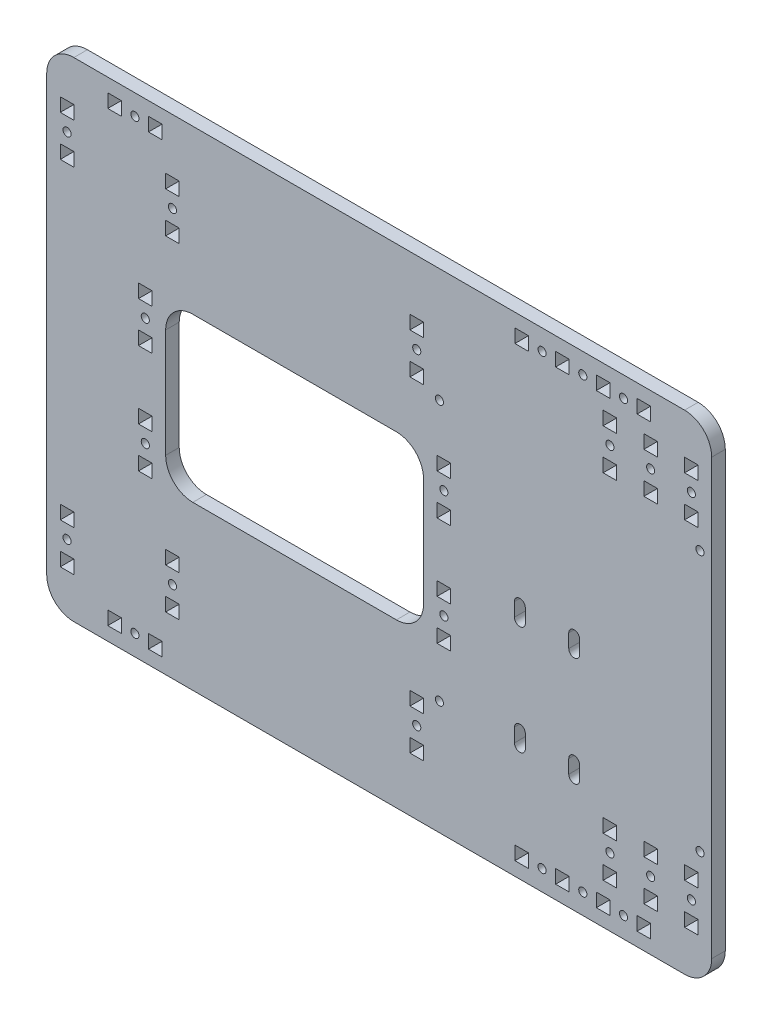
SolidWorks part; units mm, degrees
ref_plane "Front Plane" through (0, 0, 0) normal (0, 0, 1) x (1, 0, 0)
ref_plane "Top Plane" through (0, 0, 0) normal (0, 1, 0) x (1, 0, 0)
ref_plane "Right Plane" through (0, 0, 0) normal (1, 0, 0) x (0, 0, -1)
sketch "Sketch1" plane through (0, 0, 0) normal (0, 0, 1) x (1, 0, 0)
  line L0 (0, 0) -> (264.3375, 0) construction
  line L1 (-91.3244, 90) -> (153.676, 90)
  line L3 (-91.3244, -90) -> (153.676, -90)
  line L5 (23.6756, 97.7888) -> (23.6756, -107.1048) construction
  line L6 (-92.4996, 82.5) -> (92.5, 82.5) construction
  line L7 (92.5, -82.5) -> (-92.4996, -82.5) construction
  line L8 (-91.3244, 90) -> (-91.3244, -90)
  line L17 (53.355, -48) -> (53.355, 48) construction
  line L29 (53.355, -48) -> (149.355, -48) construction
  line L49 (53.355, 48) -> (149.355, 48) construction
  line L50 (149.355, -48) -> (149.355, 48) construction
  line L51 (-83.8244, 77.0051) -> (-83.8244, -67.4641) construction
  line L97 (-47.5, 30) -> (47.5, 30)
  line L98 (-47.5, 30) -> (-47.5, -30)
  line L99 (-47.5, -30) -> (47.5, -30)
  line L100 (47.5, 30) -> (47.5, -30)
  line L105 (103, -45) -> (49.07, -45) construction
  line L106 (103, -4.9002) -> (73.57, -4.9002) construction
  line L107 (103, -4.9002) -> (103, -45) construction
  line L108 (103, -7.4002) -> (103, -2.4002) construction
  line L109 (101, -7.4002) -> (101, -2.4002)
  line L110 (105, -7.4002) -> (105, -2.4002)
  line L111 (83, -7.4002) -> (83, -2.4002) construction
  line L112 (81, -7.4002) -> (81, -2.4002)
  line L113 (85, -7.4002) -> (85, -2.4002)
  line L114 (83, -47.5) -> (83, -42.5) construction
  line L115 (81, -47.5) -> (81, -42.5)
  line L116 (85, -47.5) -> (85, -42.5)
  line L117 (103, -47.5) -> (103, -42.5) construction
  line L118 (101, -47.5) -> (101, -42.5)
  line L119 (105, -47.5) -> (105, -42.5)
  line L122 (153.676, 90) -> (153.676, -90)
  line L124 (-83.8244, 65) -> (153.676, 65) construction
  line L125 (-83.8244, -65) -> (153.676, -65) construction
  line L126 (55, -20) -> (55, 20) construction
  arc A4 (101, -7.4002) -> (105, -7.4002) centre (103, -7.4002) ccw
  arc A5 (105, -2.4002) -> (101, -2.4002) centre (103, -2.4002) ccw
  arc A6 (81, -7.4002) -> (85, -7.4002) centre (83, -7.4002) ccw
  arc A7 (85, -2.4002) -> (81, -2.4002) centre (83, -2.4002) ccw
  arc A8 (81, -47.5) -> (85, -47.5) centre (83, -47.5) ccw
  arc A9 (85, -42.5) -> (81, -42.5) centre (83, -42.5) ccw
  arc A10 (101, -47.5) -> (105, -47.5) centre (103, -47.5) ccw
  arc A11 (105, -42.5) -> (101, -42.5) centre (103, -42.5) ccw
  circle A12 centre (53.355, 48) radius 1.5
  circle A13 centre (149.355, 48) radius 1.5
  circle A14 centre (149.355, -48) radius 1.5
  circle A15 centre (53.355, -48) radius 1.5
  point P21 (124, -51.7759)
  point P26 (103, -45.0347)
  point P113 (103, -4.9002)
  point P122 (83, -4.9002)
  point P129 (83, -45)
  point P136 (103, -45)
  line B0 (-63.8248, 82.5) -> (-53.8248, 82.5) construction
  line B1 (-63.8248, 85) -> (-68.8248, 85)
  line B2 (-63.8248, 85) -> (-63.8248, 80)
  line B3 (-63.8248, 80) -> (-68.8248, 80)
  line B4 (-68.8248, 85) -> (-68.8248, 80)
  line B5 (-53.8248, 85) -> (-48.8248, 85)
  line B6 (-53.8248, 85) -> (-53.8248, 80)
  line B7 (-53.8248, 80) -> (-48.8248, 80)
  line B8 (-48.8248, 85) -> (-48.8248, 80)
  line B9 (-58.8248, 82.5) -> (-58.8248, 89.4724) construction
  circle B10 centre (-58.8248, 82.5) radius 1.5
  line B11 (111.176, 82.5) -> (101.176, 82.5) construction
  line B12 (111.176, 85) -> (116.176, 85)
  line B13 (111.176, 85) -> (111.176, 80)
  line B14 (111.176, 80) -> (116.176, 80)
  line B15 (116.176, 85) -> (116.176, 80)
  line B16 (101.176, 85) -> (96.176, 85)
  line B17 (101.176, 85) -> (101.176, 80)
  line B18 (101.176, 80) -> (96.176, 80)
  line B19 (96.176, 85) -> (96.176, 80)
  line B20 (106.176, 82.5) -> (106.176, 89.4724) construction
  circle B21 centre (106.176, 82.5) radius 1.5
  line B22 (111.176, -82.5) -> (101.176, -82.5) construction
  line B23 (111.176, -85) -> (116.176, -85)
  line B24 (111.176, -85) -> (111.176, -80)
  line B25 (111.176, -80) -> (116.176, -80)
  line B26 (116.176, -85) -> (116.176, -80)
  line B27 (101.176, -85) -> (96.176, -85)
  line B28 (101.176, -85) -> (101.176, -80)
  line B29 (101.176, -80) -> (96.176, -80)
  line B30 (96.176, -85) -> (96.176, -80)
  line B31 (106.176, -82.5) -> (106.176, -89.4724) construction
  circle B32 centre (106.176, -82.5) radius 1.5
  line B33 (-63.8248, -82.5) -> (-53.8248, -82.5) construction
  line B34 (-63.8248, -85) -> (-68.8248, -85)
  line B35 (-63.8248, -85) -> (-63.8248, -80)
  line B36 (-63.8248, -80) -> (-68.8248, -80)
  line B37 (-68.8248, -85) -> (-68.8248, -80)
  line B38 (-53.8248, -85) -> (-48.8248, -85)
  line B39 (-53.8248, -85) -> (-53.8248, -80)
  line B40 (-53.8248, -80) -> (-48.8248, -80)
  line B41 (-48.8248, -85) -> (-48.8248, -80)
  line B42 (-58.8248, -82.5) -> (-58.8248, -89.4724) construction
  circle B43 centre (-58.8248, -82.5) radius 1.5
  line B44 (55, 25) -> (55, 15) construction
  line B45 (57.5, 25) -> (57.5, 30)
  line B46 (57.5, 25) -> (52.5, 25)
  line B47 (52.5, 25) -> (52.5, 30)
  line B48 (57.5, 30) -> (52.5, 30)
  line B49 (57.5, 15) -> (57.5, 10)
  line B50 (57.5, 15) -> (52.5, 15)
  line B51 (52.5, 15) -> (52.5, 10)
  line B52 (57.5, 10) -> (52.5, 10)
  line B53 (55, 20) -> (61.9724, 20) construction
  circle B54 centre (55, 20) radius 1.5
  line B55 (-55, 25) -> (-55, 15) construction
  line B56 (-57.5, 25) -> (-57.5, 30)
  line B57 (-57.5, 25) -> (-52.5, 25)
  line B58 (-52.5, 25) -> (-52.5, 30)
  line B59 (-57.5, 30) -> (-52.5, 30)
  line B60 (-57.5, 15) -> (-57.5, 10)
  line B61 (-57.5, 15) -> (-52.5, 15)
  line B62 (-52.5, 15) -> (-52.5, 10)
  line B63 (-57.5, 10) -> (-52.5, 10)
  line B64 (-55, 20) -> (-61.9724, 20) construction
  circle B65 centre (-55, 20) radius 1.5
  line B66 (55, -25) -> (55, -15) construction
  line B67 (57.5, -25) -> (57.5, -30)
  line B68 (57.5, -25) -> (52.5, -25)
  line B69 (52.5, -25) -> (52.5, -30)
  line B70 (57.5, -30) -> (52.5, -30)
  line B71 (57.5, -15) -> (57.5, -10)
  line B72 (57.5, -15) -> (52.5, -15)
  line B73 (52.5, -15) -> (52.5, -10)
  line B74 (57.5, -10) -> (52.5, -10)
  line B75 (55, -20) -> (61.9724, -20) construction
  circle B76 centre (55, -20) radius 1.5
  line B77 (-55, -25) -> (-55, -15) construction
  line B78 (-57.5, -25) -> (-57.5, -30)
  line B79 (-57.5, -25) -> (-52.5, -25)
  line B80 (-52.5, -25) -> (-52.5, -30)
  line B81 (-57.5, -30) -> (-52.5, -30)
  line B82 (-57.5, -15) -> (-57.5, -10)
  line B83 (-57.5, -15) -> (-52.5, -15)
  line B84 (-52.5, -15) -> (-52.5, -10)
  line B85 (-57.5, -10) -> (-52.5, -10)
  line B86 (-55, -20) -> (-61.9724, -20) construction
  circle B87 centre (-55, -20) radius 1.5
  line B88 (45, 65) -> (45, 55) construction
  line B89 (47.5, 65) -> (47.5, 70)
  line B90 (47.5, 65) -> (42.5, 65)
  line B91 (42.5, 65) -> (42.5, 70)
  line B92 (47.5, 70) -> (42.5, 70)
  line B93 (47.5, 55) -> (47.5, 50)
  line B94 (47.5, 55) -> (42.5, 55)
  line B95 (42.5, 55) -> (42.5, 50)
  line B96 (47.5, 50) -> (42.5, 50)
  line B97 (45, 60) -> (51.9724, 60) construction
  circle B98 centre (45, 60) radius 1.5
  line B99 (-45, 65) -> (-45, 55) construction
  line B100 (-47.5, 65) -> (-47.5, 70)
  line B101 (-47.5, 65) -> (-42.5, 65)
  line B102 (-42.5, 65) -> (-42.5, 70)
  line B103 (-47.5, 70) -> (-42.5, 70)
  line B104 (-47.5, 55) -> (-47.5, 50)
  line B105 (-47.5, 55) -> (-42.5, 55)
  line B106 (-42.5, 55) -> (-42.5, 50)
  line B107 (-47.5, 50) -> (-42.5, 50)
  line B108 (-45, 60) -> (-51.9724, 60) construction
  circle B109 centre (-45, 60) radius 1.5
  line B110 (45, -65) -> (45, -55) construction
  line B111 (47.5, -65) -> (47.5, -70)
  line B112 (47.5, -65) -> (42.5, -65)
  line B113 (42.5, -65) -> (42.5, -70)
  line B114 (47.5, -70) -> (42.5, -70)
  line B115 (47.5, -55) -> (47.5, -50)
  line B116 (47.5, -55) -> (42.5, -55)
  line B117 (42.5, -55) -> (42.5, -50)
  line B118 (47.5, -50) -> (42.5, -50)
  line B119 (45, -60) -> (51.9724, -60) construction
  circle B120 centre (45, -60) radius 1.5
  line B121 (-45, -65) -> (-45, -55) construction
  line B122 (-47.5, -65) -> (-47.5, -70)
  line B123 (-47.5, -65) -> (-42.5, -65)
  line B124 (-42.5, -65) -> (-42.5, -70)
  line B125 (-47.5, -70) -> (-42.5, -70)
  line B126 (-47.5, -55) -> (-47.5, -50)
  line B127 (-47.5, -55) -> (-42.5, -55)
  line B128 (-42.5, -55) -> (-42.5, -50)
  line B129 (-47.5, -50) -> (-42.5, -50)
  line B130 (-45, -60) -> (-51.9724, -60) construction
  circle B131 centre (-45, -60) radius 1.5
  line B132 (96.176, 82.5) -> (86.176, 82.5) construction
  line B133 (96.176, 85) -> (101.176, 85)
  line B134 (96.176, 85) -> (96.176, 80)
  line B135 (96.176, 80) -> (101.176, 80)
  line B136 (101.176, 85) -> (101.176, 80)
  line B137 (86.176, 85) -> (81.176, 85)
  line B138 (86.176, 85) -> (86.176, 80)
  line B139 (86.176, 80) -> (81.176, 80)
  line B140 (81.176, 85) -> (81.176, 80)
  line B141 (91.176, 82.5) -> (91.176, 89.4724) construction
  circle B142 centre (91.176, 82.5) radius 1.5
  line B143 (126.176, 82.5) -> (116.176, 82.5) construction
  line B144 (126.176, 85) -> (131.176, 85)
  line B145 (126.176, 85) -> (126.176, 80)
  line B146 (126.176, 80) -> (131.176, 80)
  line B147 (131.176, 85) -> (131.176, 80)
  line B148 (116.176, 85) -> (111.176, 85)
  line B149 (116.176, 85) -> (116.176, 80)
  line B150 (116.176, 80) -> (111.176, 80)
  line B151 (111.176, 85) -> (111.176, 80)
  line B152 (121.176, 82.5) -> (121.176, 89.4724) construction
  circle B153 centre (121.176, 82.5) radius 1.5
  line B154 (96.176, -82.5) -> (86.176, -82.5) construction
  line B155 (96.176, -85) -> (101.176, -85)
  line B156 (96.176, -85) -> (96.176, -80)
  line B157 (96.176, -80) -> (101.176, -80)
  line B158 (101.176, -85) -> (101.176, -80)
  line B159 (86.176, -85) -> (81.176, -85)
  line B160 (86.176, -85) -> (86.176, -80)
  line B161 (86.176, -80) -> (81.176, -80)
  line B162 (81.176, -85) -> (81.176, -80)
  line B163 (91.176, -82.5) -> (91.176, -89.4724) construction
  circle B164 centre (91.176, -82.5) radius 1.5
  line B165 (126.176, -82.5) -> (116.176, -82.5) construction
  line B166 (126.176, -85) -> (131.176, -85)
  line B167 (126.176, -85) -> (126.176, -80)
  line B168 (126.176, -80) -> (131.176, -80)
  line B169 (131.176, -85) -> (131.176, -80)
  line B170 (116.176, -85) -> (111.176, -85)
  line B171 (116.176, -85) -> (116.176, -80)
  line B172 (116.176, -80) -> (111.176, -80)
  line B173 (111.176, -85) -> (111.176, -80)
  line B174 (121.176, -82.5) -> (121.176, -89.4724) construction
  circle B175 centre (121.176, -82.5) radius 1.5
  line B176 (-83.8244, 70) -> (-83.8244, 60) construction
  line B177 (-86.3244, 70) -> (-86.3244, 75)
  line B178 (-86.3244, 70) -> (-81.3244, 70)
  line B179 (-81.3244, 70) -> (-81.3244, 75)
  line B180 (-86.3244, 75) -> (-81.3244, 75)
  line B181 (-86.3244, 60) -> (-86.3244, 55)
  line B182 (-86.3244, 60) -> (-81.3244, 60)
  line B183 (-81.3244, 60) -> (-81.3244, 55)
  line B184 (-86.3244, 55) -> (-81.3244, 55)
  line B185 (-83.8244, 65) -> (-90.7968, 65) construction
  circle B186 centre (-83.8244, 65) radius 1.5
  line B187 (-83.8244, -60) -> (-83.8244, -70) construction
  line B188 (-86.3244, -60) -> (-86.3244, -55)
  line B189 (-86.3244, -60) -> (-81.3244, -60)
  line B190 (-81.3244, -60) -> (-81.3244, -55)
  line B191 (-86.3244, -55) -> (-81.3244, -55)
  line B192 (-86.3244, -70) -> (-86.3244, -75)
  line B193 (-86.3244, -70) -> (-81.3244, -70)
  line B194 (-81.3244, -70) -> (-81.3244, -75)
  line B195 (-86.3244, -75) -> (-81.3244, -75)
  line B196 (-83.8244, -65) -> (-90.7968, -65) construction
  circle B197 centre (-83.8244, -65) radius 1.5
  line B198 (146.176, 70) -> (146.176, 60) construction
  line B199 (143.676, 70) -> (143.676, 75)
  line B200 (143.676, 70) -> (148.676, 70)
  line B201 (148.676, 70) -> (148.676, 75)
  line B202 (143.676, 75) -> (148.676, 75)
  line B203 (143.676, 60) -> (143.676, 55)
  line B204 (143.676, 60) -> (148.676, 60)
  line B205 (148.676, 60) -> (148.676, 55)
  line B206 (143.676, 55) -> (148.676, 55)
  line B207 (146.176, 65) -> (139.2036, 65) construction
  circle B208 centre (146.176, 65) radius 1.5
  line B209 (146.176, -60) -> (146.176, -70) construction
  line B210 (143.676, -60) -> (143.676, -55)
  line B211 (143.676, -60) -> (148.676, -60)
  line B212 (148.676, -60) -> (148.676, -55)
  line B213 (143.676, -55) -> (148.676, -55)
  line B214 (143.676, -70) -> (143.676, -75)
  line B215 (143.676, -70) -> (148.676, -70)
  line B216 (148.676, -70) -> (148.676, -75)
  line B217 (143.676, -75) -> (148.676, -75)
  line B218 (146.176, -65) -> (139.2036, -65) construction
  circle B219 centre (146.176, -65) radius 1.5
  line B220 (131.176, -60) -> (131.176, -70) construction
  line B221 (128.676, -60) -> (128.676, -55)
  line B222 (128.676, -60) -> (133.676, -60)
  line B223 (133.676, -60) -> (133.676, -55)
  line B224 (128.676, -55) -> (133.676, -55)
  line B225 (128.676, -70) -> (128.676, -75)
  line B226 (128.676, -70) -> (133.676, -70)
  line B227 (133.676, -70) -> (133.676, -75)
  line B228 (128.676, -75) -> (133.676, -75)
  line B229 (131.176, -65) -> (124.2036, -65) construction
  circle B230 centre (131.176, -65) radius 1.5
  line B231 (116.176, -60) -> (116.176, -70) construction
  line B232 (113.676, -60) -> (113.676, -55)
  line B233 (113.676, -60) -> (118.676, -60)
  line B234 (118.676, -60) -> (118.676, -55)
  line B235 (113.676, -55) -> (118.676, -55)
  line B236 (113.676, -70) -> (113.676, -75)
  line B237 (113.676, -70) -> (118.676, -70)
  line B238 (118.676, -70) -> (118.676, -75)
  line B239 (113.676, -75) -> (118.676, -75)
  line B240 (116.176, -65) -> (109.2036, -65) construction
  circle B241 centre (116.176, -65) radius 1.5
  line B242 (131.176, 70) -> (131.176, 60) construction
  line B243 (128.676, 70) -> (128.676, 75)
  line B244 (128.676, 70) -> (133.676, 70)
  line B245 (133.676, 70) -> (133.676, 75)
  line B246 (128.676, 75) -> (133.676, 75)
  line B247 (128.676, 60) -> (128.676, 55)
  line B248 (128.676, 60) -> (133.676, 60)
  line B249 (133.676, 60) -> (133.676, 55)
  line B250 (128.676, 55) -> (133.676, 55)
  line B251 (131.176, 65) -> (124.2036, 65) construction
  circle B252 centre (131.176, 65) radius 1.5
  line B253 (116.176, 70) -> (116.176, 60) construction
  line B254 (113.676, 70) -> (113.676, 75)
  line B255 (113.676, 70) -> (118.676, 70)
  line B256 (118.676, 70) -> (118.676, 75)
  line B257 (113.676, 75) -> (118.676, 75)
  line B258 (113.676, 60) -> (113.676, 55)
  line B259 (113.676, 60) -> (118.676, 60)
  line B260 (118.676, 60) -> (118.676, 55)
  line B261 (113.676, 55) -> (118.676, 55)
  line B262 (116.176, 65) -> (109.2036, 65) construction
  circle B263 centre (116.176, 65) radius 1.5
  dimension "D22" = 45
  dimension "D23" = 5
  dimension "D8" = 3
  dimension "D24" = 2
  dimension "D1" = 165
  dimension "D2" = 7.5
  dimension "D4" = 32.4996
  dimension "D5" = 32.5
  dimension "D6" = 96
  dimension "D7" = 96
  dimension "D9" = 115
  dimension "D10" = 23.6756
  dimension "D11" = 28
  dimension "D12" = 47.5
  dimension "D13" = 7.5
  dimension "D14" = 25
  dimension "D15" = 40
  dimension "D16" = 95
  dimension "D17" = 60
  dimension "D18" = 7.5
  dimension "D19" = 15
  dimension "D20" = 15
  dimension "D21" = 7.5
  dimension "D25" = 2
  dimension "D27" = 20
  dimension "D33" = 60
  dimension "D26" = 2
sketch_block_instance "Trou M3 plots 5mm-1"
sketch_block "Trou M3 plots 5mm" parameters "D2"=3, "D1"=5, "D3"=5, "D4"=10
sketch_block_instance "Trou M3 plots 5mm-3"
sketch_block_instance "Trou M3 plots 5mm-4"
sketch_block_instance "Trou M3 plots 5mm-5"
sketch_block_instance "Trou M3 plots 5mm-7"
sketch_block_instance "Trou M3 plots 5mm-8"
sketch_block_instance "Trou M3 plots 5mm-9"
sketch_block_instance "Trou M3 plots 5mm-10"
sketch_block_instance "Trou M3 plots 5mm-11"
sketch_block_instance "Trou M3 plots 5mm-12"
sketch_block_instance "Trou M3 plots 5mm-13"
sketch_block_instance "Trou M3 plots 5mm-14"
sketch_block_instance "Trou M3 plots 5mm-15"
sketch_block_instance "Trou M3 plots 5mm-16"
sketch_block_instance "Trou M3 plots 5mm-18"
sketch_block_instance "Trou M3 plots 5mm-19"
sketch_block_instance "Trou M3 plots 5mm-20"
sketch_block_instance "Trou M3 plots 5mm-21"
sketch_block_instance "Trou M3 plots 5mm-22"
sketch_block_instance "Trou M3 plots 5mm-23"
sketch_block_instance "Trou M3 plots 5mm-24"
sketch_block_instance "Trou M3 plots 5mm-25"
sketch_block_instance "Trou M3 plots 5mm-26"
sketch_block_instance "Trou M3 plots 5mm-27"
extrude "Boss-Extrude1" add sketch "Sketch1" along normal blind 5 contours L122 L1 L8 L3 B175 B169 B166 B167 B168 B164 B144 B147 B146 B145 B142 B140 B137 B138 B139 B131 B125 B122 B123 B124 B111 B114 B113 B112 B109 B107 B104 B105 B106 B98 B92 B89 B90 B91 region at (31.1758, 86.9598, 0)
fillet "Fillet1" radius 10 8 edges at (-91.3244, 90, 2.5) (-91.3244, -90, 2.5) (153.676, 90, 2.5) (153.676, -90, 2.5) (-47.5, -30, 2.5) (-47.5, 30, 2.5) (47.5, 30, 2.5) (47.5, -30, 2.5)
